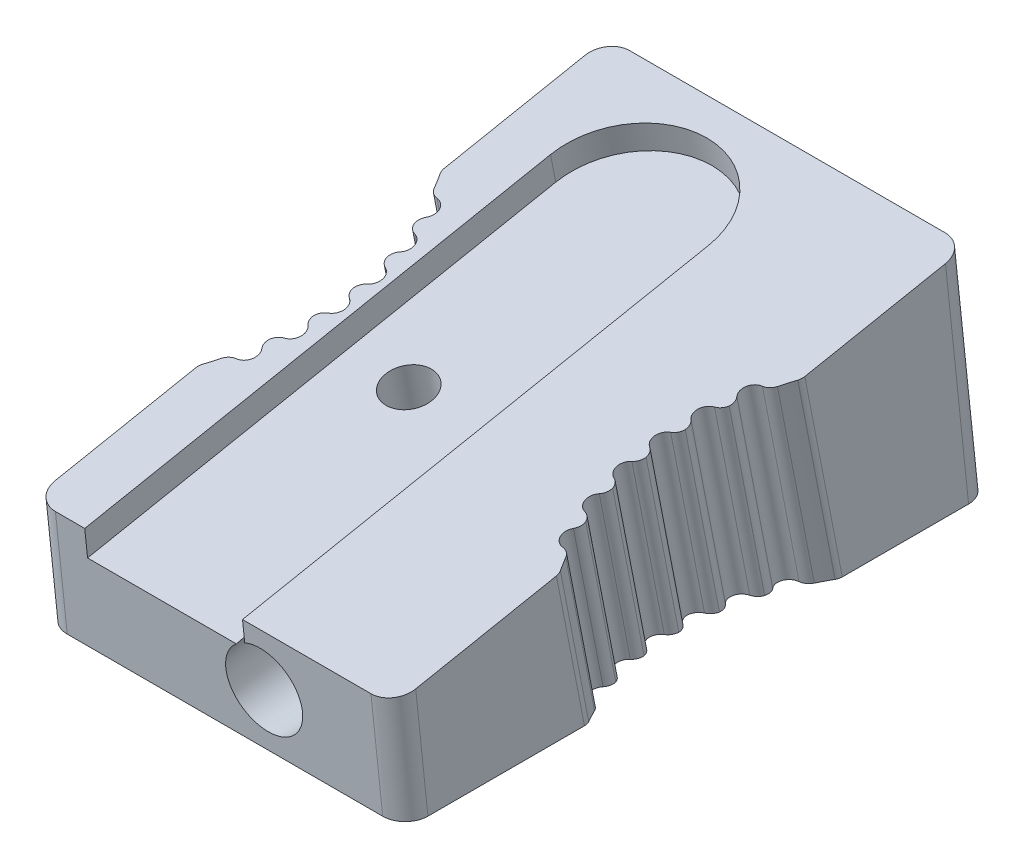
SolidWorks part; units mm, degrees
material "1060 Alloy"
ref_plane "Front Plane" through (0, 0, 0) normal (0, 0, 1) x (1, 0, 0)
ref_plane "Top Plane" through (0, 0, 0) normal (0, 1, 0) x (1, 0, 0)
ref_plane "Right Plane" through (0, 0, 0) normal (1, 0, 0) x (0, 0, -1)
sketch "Sketch1" plane through (0, 0, 0) normal (1, 0, 0) x (0, 0, -1)
  line L0 (0, 0) -> (-26, 0)
  line L1 (-26, 0) -> (-26.5226, 4.9726)
  line L2 (-26.5226, 4.9726) -> (-1.0453, 9.9452)
  line L3 (-1.0453, 9.9452) -> (0, 0)
  dimension "D1" = 26
  dimension "D2" = 84
  dimension "D3" = 10
  dimension "D4" = 5
extrude "Extrude 1" add sketch "Sketch1" along normal mid plane 16
sketch "Sketch2" plane through (0, 9.7768, 1.9082) normal (0, 0.9815, 0.1916) x (1, 0, 0)
  line L0 (0, 0.8792) -> (0, -25.0789) construction
  line L1 (8, 0.8792) -> (-8, 0.8792) construction
  line L2 (8, -25.0789) -> (-8, -25.0789) construction
  line L3 (-8, 0.8792) -> (-8, -25.0789) construction
  line L4 (-8, -6.6208) -> (-8, -17.5789)
  line L5 (8, -6.6208) -> (8, -17.5789)
  arc A0 (-8, -6.6208) -> (-8, -17.5789) centre (-17.2567, -12.0998) cw
  arc A1 (8, -6.6208) -> (8, -17.5789) centre (17.2567, -12.0998) ccw
  dimension "D3" = 13
  dimension "D1" = 7.5
  dimension "D2" = 7.5
extrude "Extrude 2" cut sketch "Sketch2" against normal blind 16
sketch "Sketch3" plane through (0, 9.7768, 1.9082) normal (0, 0.9815, 0.1916) x (1, 0, 0)
  line L0 (0, 0.8792) -> (0, -25.0789) construction
  line L1 (8, 0.8792) -> (-8, 0.8792) construction
  line L2 (8, -25.0789) -> (-8, -25.0789) construction
  circle A0 centre (-7.2709, -8.101) radius 0.5
  arc A1 (-8, -17.5789) -> (-8, -6.6208) centre (-17.2567, -12.0998) ccw construction
  circle A2 centre (-6.7768, -9.6753) radius 0.5
  circle A3 centre (-6.5293, -11.3066) radius 0.5
  circle A4 centre (-6.5342, -12.9566) radius 0.5
  circle A5 centre (-6.7914, -14.5864) radius 0.5
  circle A6 centre (-7.2948, -16.1577) radius 0.5
  circle A7 centre (7.2948, -16.1577) radius 0.5
  circle A8 centre (6.7914, -14.5864) radius 0.5
  circle A9 centre (6.5342, -12.9566) radius 0.5
  circle A10 centre (6.5293, -11.3066) radius 0.5
  circle A11 centre (6.7768, -9.6753) radius 0.5
  circle A12 centre (7.2709, -8.101) radius 0.5
  dimension "D1" = 1
  dimension "D2" = 1.65
  dimension "D3" = 1.65
  dimension "D4" = 1.65
  dimension "D5" = 1.65
  dimension "D6" = 1.65
  dimension "D7" = 1.65
extrude "Extrude 3" cut sketch "Sketch3" against normal blind 16
ref_plane "Plane1" through (2, 0, 0) normal (1, 0, 0) x (0, 0, -1)
sketch "Sketch4" plane through (2, 0, 0) normal (1, 0, 0) x (0, 0, -1)
  line L0 (-26.2613, 2.4863) -> (-0.5226, 4.9726) construction
  line L1 (-26.5226, 4.9726) -> (-26, 0) construction
  line L2 (0, 0) -> (-1.0453, 9.9452) construction
  line L5 (-27.5172, 4.8681) -> (-26.9945, -0.1045)
  line L6 (-27.4251, 3.9924) -> (-27.2567, 2.3902)
  line L7 (-27.2567, 2.3902) -> (0.4728, 5.0688)
  line L8 (0.9945, 0.1045) -> (-0.0508, 10.0497)
  line L9 (0.4728, 5.0688) -> (0.0453, 9.1353)
  line L10 (-27.4251, 3.9924) -> (0.0453, 9.1353)
  point P15 (-26.439, 4.177)
  point P16 (-0.9408, 8.9507)
  dimension "D3" = 4
  dimension "D4" = 1.7
  dimension "D1" = 1
  dimension "D2" = 1
revolve "Extrude 4" cut sketch "Sketch4" angle 360 about L0
sketch "Sketch8" plane through (0, 9.7768, 1.9082) normal (0, 0.9815, 0.1916) x (1, 0, 0)
  line L0 (-5.7, -25.5185) -> (-5.7, -4.0208)
  line L1 (8, -25.5185) -> (-8, -25.5185) construction
  line L2 (1.3, -4.0208) -> (1.3, -25.5185)
  line L3 (1.3, -25.5185) -> (-5.7, -25.5185)
  line L4 (-8, -17.5789) -> (-8, -25.0789) construction
  line L5 (8, 0.8792) -> (-8, 0.8792) construction
  arc A0 (-5.7, -4.0208) -> (1.3, -4.0208) centre (-2.2, -4.0208) cw
  dimension "D1" = 2.3
  dimension "D2" = 7
  dimension "D3" = 1.4
extrude "Extrude 5" cut sketch "Sketch8" against normal blind 1.2
hole_wizard "Extrude 6" positions "Sketch9" profile "Sketch10" tap size "M2.5x0.45" standard "ANSI Metric"
sketch "Sketch9" plane through (0, 8.599, 1.6783) normal (0, 0.9815, 0.1916) x (1, 0, 0)
  line L0 (-5.7, -4.0208) -> (-5.7, -25.1848) construction
  line L1 (8, -25.5185) -> (-8, -25.5185) construction
  point P0 (-2.9, -13.5185)
  dimension "D1" = 2.8
  dimension "D2" = 12
sketch "Sketch10" plane through (-2.9, 6.0094, 14.9465) normal (1, 0, 0) x (0, -0.1916, 0.9815)
  line L0 (0, 0) -> (0, 4.6159)
  line L1 (0, 4.6159) -> (1.025, 4)
  line L2 (1.025, 4) -> (1.025, 0)
  line L5 (1.025, 0) -> (0, 0)
  line L10 (0, 4.6159) -> (-1.025, 4) construction
  line L11 (0, -6.35) -> (0, 107.95) construction
  dimension "Tap Drill Dia." = 2.05
  dimension "Tap Drill Depth" = 4
  dimension "Drill Angle" = 118
cosmetic thread "Hole Thread1"
fillet "Fillet1" radius 1 4 edges at (8, 4.9726, 0.5226) (-8, 4.9726, 0.5226) (8, 2.4863, 26.2613) (-8, 2.4863, 26.2613)
fillet "Fillet2" radius 0.5 28 edges at (-7.4675, 4.1565, 8.5967) (-7.0959, 4.0676, 9.5249) (-6.9008, 4.0081, 10.1466) (-6.6755, 3.9148, 11.1208) (-6.5777, 3.8531, 11.7649) (-6.504, 3.7576, 12.7621) (-6.5059, 3.6952, 13.4137) (-6.5856, 3.5998, 14.4104) (-6.6871, 3.5381, 15.054) (-6.9182, 3.445, 16.0268) (-7.117, 3.3855, 16.6473) (-7.4941, 3.2969, 17.5733) (-8, 3.2047, 18.5361) (8, 3.2047, 18.5361) (7.4941, 3.2969, 17.5733) (7.117, 3.3855, 16.6473) (6.9182, 3.445, 16.0268) (6.6871, 3.5381, 15.054) (6.5856, 3.5998, 14.4104) (6.5059, 3.6952, 13.4137) (6.504, 3.7576, 12.7621) (6.5777, 3.8531, 11.7649) (6.6755, 3.9148, 11.1208) (6.9008, 4.0081, 10.1466) (7.0959, 4.0676, 9.5249) (7.4675, 4.1565, 8.5967) (8, 4.2542, 7.5761) (-8, 4.2542, 7.5761)
